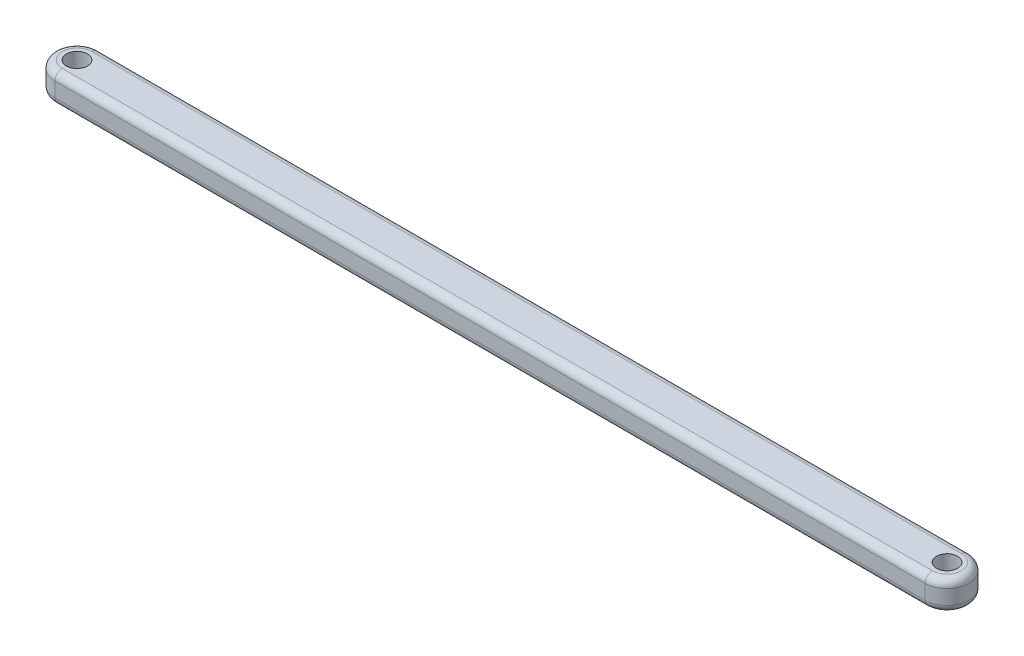
SolidWorks part; units mm, degrees
ref_plane "Front Plane" through (0, 0, 0) normal (0, 0, 1) x (1, 0, 0)
ref_plane "Top Plane" through (0, 0, 0) normal (0, 1, 0) x (1, 0, 0)
ref_plane "Right Plane" through (0, 0, 0) normal (1, 0, 0) x (0, 0, -1)
sketch "Sketch1" plane through (0, 0, 0) normal (0, 1, 0) x (1, 0, 0)
  line L0 (0, 0) -> (188.9125, 0) construction
  line L1 (0, 4.7625) -> (188.9125, 4.7625)
  line L2 (0, -4.7625) -> (188.9125, -4.7625)
  arc A0 (0, 4.7625) -> (0, -4.7625) centre (0, 0) ccw
  arc A1 (188.9125, -4.7625) -> (188.9125, 4.7625) centre (188.9125, 0) ccw
  point P3 (94.4562, 0)
  dimension "D1" = 188.9125
  dimension "D2" = 9.525
extrude "Boss-Extrude1" add sketch "Sketch1" along normal mid plane 6.35
sketch "Sketch2" plane through (0, 3.175, 0) normal (0, 1, 0) x (1, 0, 0)
  circle A0 centre (0, 0) radius 2.286
  circle A1 centre (188.9125, 0) radius 2.286
  dimension "D1" = 4.572
extrude "Cut-Extrude1" cut sketch "Sketch2" against normal through all
fillet "Fillet1" radius 1.5875 8 edges at (193.675, -3.175, 0) (94.4562, -3.175, 4.7625) (-4.7625, -3.175, 0) (193.675, 3.175, 0) (94.4562, 3.175, 4.7625) (-4.7625, 3.175, 0) (94.4562, -3.175, -4.7625) (94.4562, 3.175, -4.7625)
